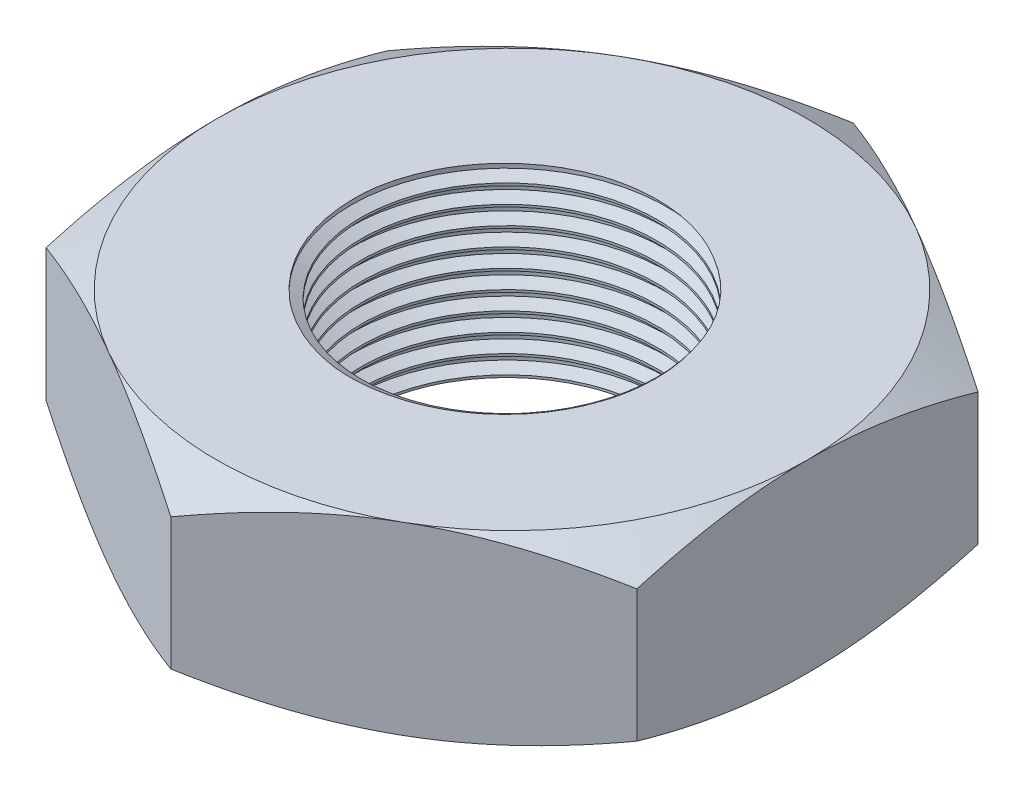
SolidWorks part; units mm, degrees
ref_plane "Front Plane" through (0, 0, 0) normal (0, 0, 1) x (1, 0, 0)
ref_plane "Top Plane" through (0, 0, 0) normal (0, 1, 0) x (1, 0, 0)
ref_plane "Right Plane" through (0, 0, 0) normal (1, 0, 0) x (0, 0, -1)
sketch "Sketch1" plane through (0, 0, 0) normal (0, 1, 0) x (1, 0, 0)
  line L1 (0, 27.7128) -> (-24, 13.8564)
  line L2 (-24, 13.8564) -> (-24, -13.8564)
  line L3 (-24, -13.8564) -> (0, -27.7128)
  line L4 (0, -27.7128) -> (24, -13.8564)
  line L5 (24, -13.8564) -> (24, 13.8564)
  line L6 (24, 13.8564) -> (0, 27.7128)
  circle A0 centre (0, 0) radius 24 construction
  circle A1 centre (0, 0) radius 12
  dimension "D2" = 24
  dimension "D1" = 48
extrude "Boss-Extrude1" add sketch "Sketch1" along normal mid plane 15
sketch "Sketch2" plane through (0, 7.5, 0) normal (0, 1, 0) x (1, 0, 0)
  line L0 (-24, 13.8564) -> (-24, -13.8564) construction
  circle A0 centre (0, 0) radius 24
extrude "Cut-Extrude1" cut sketch "Sketch2" against normal through all both draft 60 and the other way through all flip side to cut
mirror "Mirror1" about plane through (0, 0, 0) normal (0, 1, 0) of "Cut-Extrude1"
thread "Thread1" pitch 1.5 method cut trim with start face yes trim with end face yes profile "Thread Profile1" start angle 0, offset 5, length 27, pitch 1.5, diameter 24
ref_plane "Plane1" through (-12, 12.5, 0) normal (0, 0, -1) x (1, 0, 0)
sketch "Thread Profile1" plane through (-12, 12.5, 0) normal (0, 0, -1) x (1, 0, 0)
  line L0 (0, 0) -> (0, 1.5) construction
  line L11 (0, 0) -> (0, 1.3125)
  line L12 (0, 1.3125) -> (-0.8119, 0.8437)
  line L13 (-0.8119, 0.8437) -> (-0.8119, 0.4687)
  line L15 (-0.8119, 0.4687) -> (0, 0)
  line L17 (-0.8119, 0.6562) -> (0, 0.6562) construction
  point P2 (0, 0)
  dimension "Pitch" = 1.5
  dimension "Profile_Angle" = 60
  dimension "Profile_Land" = 0.375
  dimension "Profile_Height" = 0.8119
